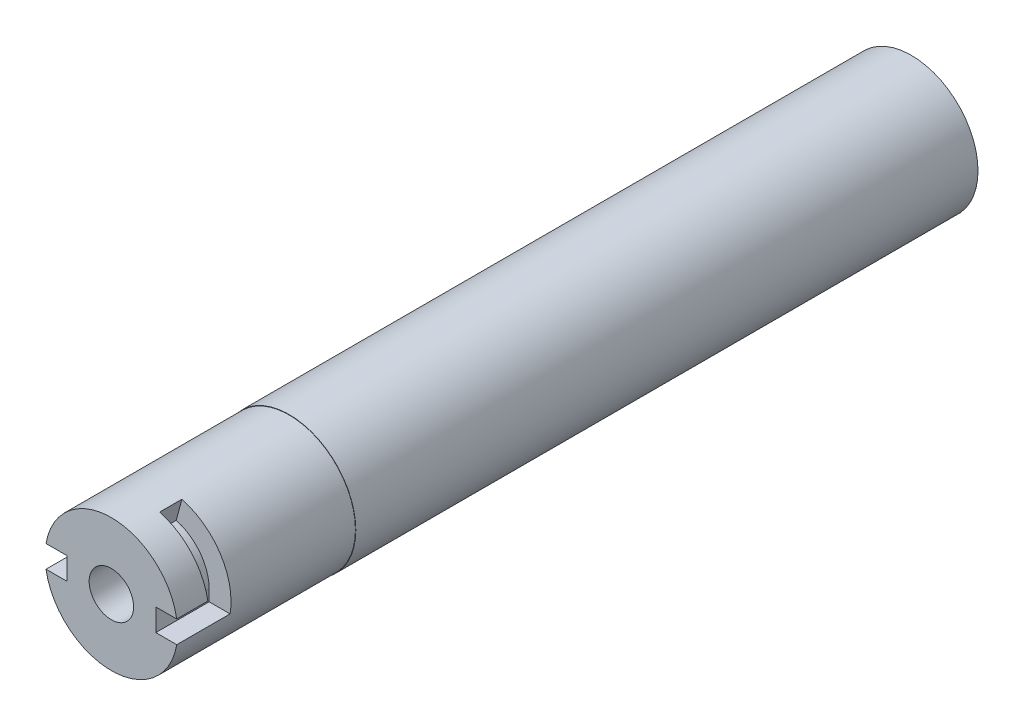
SolidWorks part; units mm, degrees
ref_plane "Front Plane" through (0, 0, 0) normal (0, 0, 1) x (1, 0, 0)
ref_plane "Top Plane" through (0, 0, 0) normal (0, 1, 0) x (1, 0, 0)
ref_plane "Right Plane" through (0, 0, 0) normal (1, 0, 0) x (0, 0, -1)
sketch "Sketch1" plane through (0, 0, 0) normal (0, 0, 1) x (1, 0, 0)
  circle A0 centre (0, 0) radius 9.525
  dimension "D1" = 19.05
extrude "Boss-Extrude1" add sketch "Sketch1" along normal blind 114.3
sketch "Sketch2" plane through (0, 0, 0) normal (0, 0, -1) x (-1, 0, 0)
  circle A0 centre (0, 0) radius 5.5562
  dimension "D1" = 11.1125
extrude "Cut-Extrude1" cut sketch "Sketch2" against normal offset from surface (101.6 mm away) 12.7 up to face at (9.525, 0, 114.3)
sketch "Sketch3" plane through (0, 0, 114.3) normal (0, 0, 1) x (1, 0, 0)
  circle A0 centre (0, 0) radius 3.175
  dimension "D1" = 6.35
extrude "Cut-Extrude2" cut sketch "Sketch3" against normal blind 114.3
sketch "Sketch5" plane through (0, 0, 114.3) normal (0, 0, 1) x (1, 0, 0)
  line L0 (9.3918, 1.5875) -> (6.35, 1.5875)
  line L1 (6.35, 1.5875) -> (6.35, -1.5875)
  line L2 (6.35, -1.5875) -> (9.3918, -1.5875)
  line L3 (0, 0) -> (9.525, 0) construction
  line L4 (0, 0) -> (0, -9.525) construction
  line L5 (-9.3918, 1.5875) -> (-6.35, 1.5875)
  line L6 (-6.35, -1.5875) -> (-9.3918, -1.5875)
  line L7 (-6.35, 1.5875) -> (-6.35, -1.5875)
  circle A1 centre (0, 0) radius 9.525
  circle A2 centre (0, 0) radius 9.525
  point P5 (6.35, 0)
  circle M8 centre (0, 0) radius 9.525
  dimension "D2" = 3.175
  dimension "D3" = 3.175
  dimension "D1" = 0
extrude "Cut-Extrude8" cut sketch "Sketch5" against normal blind 7.62 contours L1 L2 L0 M8 | L7 L5 L6 M8 region at (7.9156, 0, 114.3) region at (-7.9156, 0, 114.3)
sketch "Sketch6" plane through (0, 0, 114.3) normal (0, 0, 1) x (1, 0, 0)
  circle A0 centre (0, 0) radius 9.525
sketch "Sketch7" plane through (0, 0, 0) normal (0, 1, 0) x (1, 0, 0)
  line L1 (0, 0) -> (0, -114.3) construction
  line L2 (9.3918, -106.68) -> (6.35, -106.68) construction
  line L3 (9.3918, -106.68) -> (6.35, -106.68)
  line L4 (9.525, -109.855) -> (9.525, -106.68)
  line L5 (9.525, -106.68) -> (9.3918, -106.68)
  line L6 (6.35, -106.68) -> (6.35, -109.855)
  line L7 (6.35, -109.855) -> (9.525, -109.855)
  line L8 (-9.525, -114.3) -> (9.525, -114.3) construction
  line L9 (-6.35, -109.855) -> (-9.525, -109.855)
  line L10 (-6.35, -106.68) -> (-6.35, -109.855)
  line L11 (-9.525, -106.68) -> (-9.3918, -106.68)
  line L12 (-9.525, -109.855) -> (-9.525, -106.68)
  line L13 (-9.3918, -106.68) -> (-6.35, -106.68)
  point P11 (0, 0)
  dimension "D1" = 3.175
ref_axis "Axis1" through (0, 0, 114.3) along (0, 0, -1)
revolve "Cut-Revolve1" cut sketch "Sketch7" angle 75 about L1
sketch "Sketch8" plane through (0, 0, 114.3) normal (0, 0, 1) x (1, 0, 0)
  circle A0 centre (0, 0) radius 9.4742
  circle A1 centre (0, 0) radius 9.525 construction
  circle A2 centre (0, 0) radius 9.525
  dimension "D1" = 18.9484
extrude "Cut-Extrude10" cut sketch "Sketch8" against normal blind 25.4
